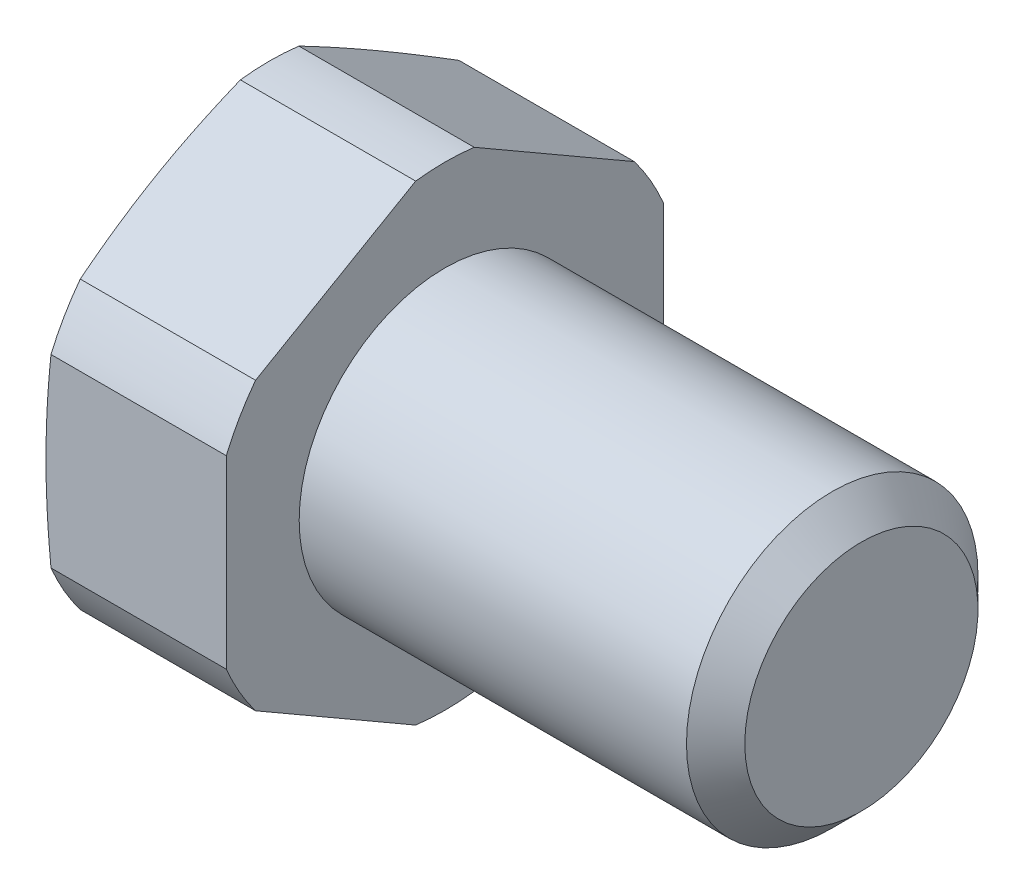
SolidWorks part; units mm, degrees
material "AISI 1020"
ref_plane "Спереди" through (0, 0, 0) normal (0, 0, 1) x (1, 0, 0)
ref_plane "Сверху" through (0, 0, 0) normal (0, 1, 0) x (1, 0, 0)
ref_plane "Справа" through (0, 0, 0) normal (1, 0, 0) x (0, 0, -1)
sketch "Эскиз1" plane through (0, 0, 0) normal (0, 0, 1) x (1, 0, 0)
  line L0 (-1000, 0) -> (49000, 0) construction
  line L1 (-8.8, 0) -> (-8.8, 9.975)
  line L2 (-8.8, 9.975) -> (-8.4182, 11.4)
  line L3 (-8.4182, 11.4) -> (0, 11.4)
  line L4 (0, 11.4) -> (0, 7)
  line L5 (0, 7) -> (18.6, 7)
  line L6 (20, 5.6) -> (20, 0)
  line L7 (20, 7) -> (21, 8.7321) construction
  line L8 (21, 8.7321) -> (22, 7) construction
  line L9 (22, 7) -> (20, 7) construction
  line L10 (21, 8.7321) -> (21, 7) construction
  line L11 (21, 8.7321) -> (1, 8.7321) construction
  line L12 (18.6, 7) -> (20, 5.6)
  line L13 (20, 7) -> (19.3, 6.3) construction
  line L14 (-8.8, 9.975) -> (-29.8, 9.975) construction
  line L15 (-8.8, 0) -> (20, 0)
  dimension "D1" = 1.4
  dimension "D2" = 15
revolve "Повернуть1" add sketch "Эскиз1" angle 360 about L0
cosmetic thread "Условное изображение резьбы1" parameters "D1"=20, "D2"=10.5359
sketch "Эскиз2" plane through (-8.8, 0, 0) normal (-1, 0, 0) x (0, 0, 1)
  line L1 (0, 12.1244) -> (-10.5, 6.0622)
  line L2 (-10.5, 6.0622) -> (-10.5, -6.0622)
  line L3 (-10.5, -6.0622) -> (0, -12.1244)
  line L4 (0, -12.1244) -> (10.5, -6.0622)
  line L5 (10.5, -6.0622) -> (10.5, 6.0622)
  line L6 (10.5, 6.0622) -> (0, 12.1244)
  circle A0 centre (0, 0) radius 10.5 construction
  dimension "D1" = 21
extrude "Вырез-Вытянуть1" cut sketch "Эскиз2" against normal up to surface (28.8 mm away) flip side to cut up to face at (20, 0, 5.6)
equation "\"D1@Эскиз1\"=\"_d_@Эскиз1\"/10"
equation "\"D@Эскиз1\"=\"S_@Эскиз1\"*0.95"
equation "\"D1@Эскиз2\"=\"S_@Эскиз1\""
equation "\"D1@Условное изображение резьбы1\"=\"b_@Эскиз1\""
equation "\"D2@Условное изображение резьбы1\"=\"_d_@Эскиз1\"-\"dr@Эскиз1\"*2"
